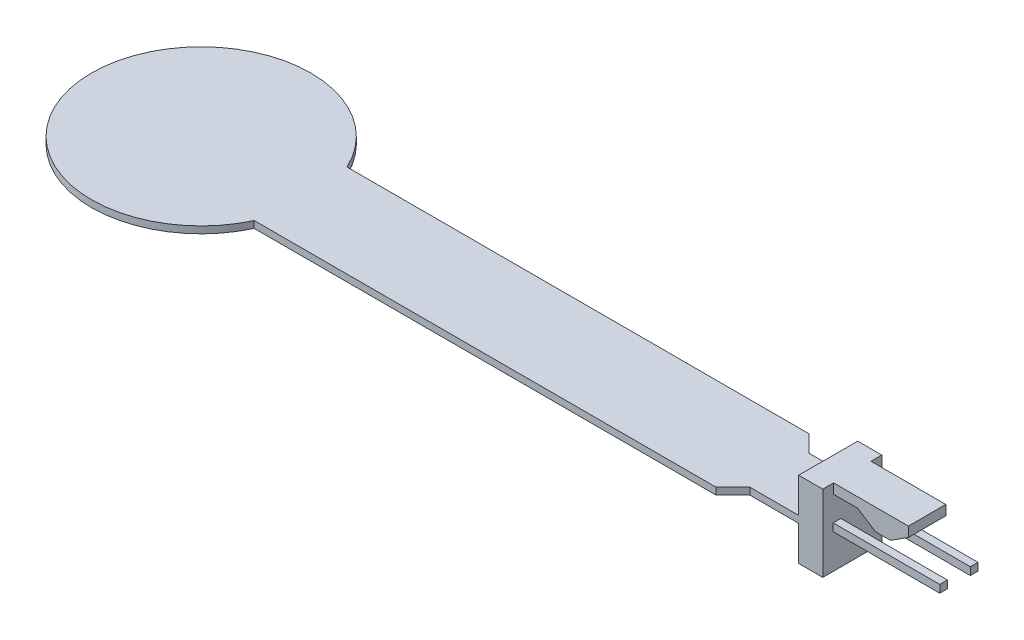
SolidWorks part; units mm, degrees
ref_plane "Front Plane" through (0, 0, 0) normal (0, 0, 1) x (1, 0, 0)
ref_plane "Top Plane" through (0, 0, 0) normal (0, 1, 0) x (1, 0, 0)
ref_plane "Right Plane" through (0, 0, 0) normal (1, 0, 0) x (0, 0, -1)
sketch "Sketch1" plane through (0, 0, 0) normal (0, 1, 0) x (1, 0, 0)
  line L0 (0, 0) -> (46.5988, 0) construction
  line L1 (8.2565, 3.85) -> (46.5988, 3.85)
  line L3 (8.2565, -3.85) -> (46.5988, -3.85)
  line L4 (46.5988, 3.85) -> (46.5988, -3.85) construction
  line L5 (0, 9.11) -> (0, -9.11) construction
  line L6 (46.5988, 3.85) -> (47.9988, 2.45)
  line L7 (47.9988, 2.45) -> (52.06, 2.45)
  line L8 (52.06, 2.45) -> (52.06, -2.45)
  line L9 (52.06, -2.45) -> (47.9988, -2.45)
  line L10 (47.9988, -2.45) -> (46.5988, -3.85)
  line L11 (46.5988, 0) -> (52.06, 0) construction
  line L12 (0, 0) -> (-9.11, 0) construction
  arc A0 (8.2565, 3.85) -> (8.2565, -3.85) centre (0, 0) ccw
  dimension "D1" = 18.22
  dimension "D3" = 61.17
  dimension "D2" = 7.7
  dimension "D4" = 4.9
  dimension "D5" = 45
extrude "Boss-Extrude1" add sketch "Sketch1" along normal mid plane 0.57
sketch "Sketch2" plane through (52.06, 0, 0) normal (1, 0, 0) x (0, 0, -1)
  line L0 (-2.45, -3.175) -> (2.45, 3.175) construction
  line L1 (-2.45, -3.175) -> (2.45, -3.175)
  line L2 (-2.45, -3.175) -> (-2.45, 3.175)
  line L3 (-2.45, 3.175) -> (2.45, 3.175)
  line L4 (2.45, -3.175) -> (2.45, 3.175)
  point P4 (0, 0)
  dimension "D1" = 6.35
  dimension "D2" = 4.9
extrude "Boss-Extrude2" add sketch "Sketch2" along normal blind 2
sketch "Sketch3" plane through (0, 0, 0) normal (0, 0, 1) x (1, 0, 0)
  line L0 (54.06, 3.175) -> (60.27, 3.175)
  line L1 (60.27, 3.175) -> (60.27, 2.355)
  line L2 (60.27, 2.355) -> (58.79, 1.405)
  line L3 (58.79, 1.405) -> (57.54, 1.405)
  line L4 (57.54, 1.405) -> (56.06, 2.355)
  line L5 (56.06, 2.355) -> (54.06, 2.355)
  line L6 (54.06, 3.175) -> (54.06, -3.175) construction
  line L7 (54.06, 2.355) -> (54.06, 3.175)
  line L8 (52.06, 3.175) -> (52.06, 0.285) construction
  line L9 (56.06, 2.355) -> (60.27, 2.355) construction
  line L10 (58.165, 1.405) -> (58.165, 2.355) construction
  dimension "D1" = 8.21
  dimension "D2" = 0.82
  dimension "D3" = 1.77
  dimension "D4" = 2
  dimension "D5" = 1.25
extrude "Boss-Extrude3" add sketch "Sketch3" along normal mid plane 3.11
sketch "Sketch4" plane through (54.06, 0, 0) normal (1, 0, 0) x (0, 0, -1)
  line L0 (-2.45, 0) -> (2.45, 0) construction
  line L1 (2.45, 0.285) -> (2.45, -0.285) construction
  line L2 (-0.9525, -0.3175) -> (0.9525, -0.3175) construction
  line L3 (-1.5875, -0.3175) -> (-0.9525, -0.3175)
  line L4 (-1.5875, -0.3175) -> (-1.5875, 0.3175)
  line L5 (-1.5875, 0.3175) -> (-0.9525, 0.3175)
  line L6 (-0.9525, -0.3175) -> (-0.9525, 0.3175)
  line L7 (-1.5875, -0.3175) -> (-0.9525, 0.3175) construction
  line L8 (-1.5875, 0.3175) -> (-0.9525, -0.3175) construction
  line L9 (0.9525, -0.3175) -> (1.5875, -0.3175)
  line L10 (0.9525, -0.3175) -> (0.9525, 0.3175)
  line L11 (0.9525, 0.3175) -> (1.5875, 0.3175)
  line L12 (1.5875, -0.3175) -> (1.5875, 0.3175)
  line L13 (0.9525, -0.3175) -> (1.5875, 0.3175) construction
  line L14 (0.9525, 0.3175) -> (1.5875, -0.3175) construction
  line L15 (0, 0) -> (0, -0.3175) construction
  point P0 (-1.27, 0)
  point P6 (0, 0)
  point P12 (1.27, 0)
  dimension "D1" = 0.635
  dimension "D2" = 2.54
extrude "Boss-Extrude4" add sketch "Sketch4" along normal offset from surface (8.85 mm away) 10.85 up to face at (52.06, 1.73, 0)
